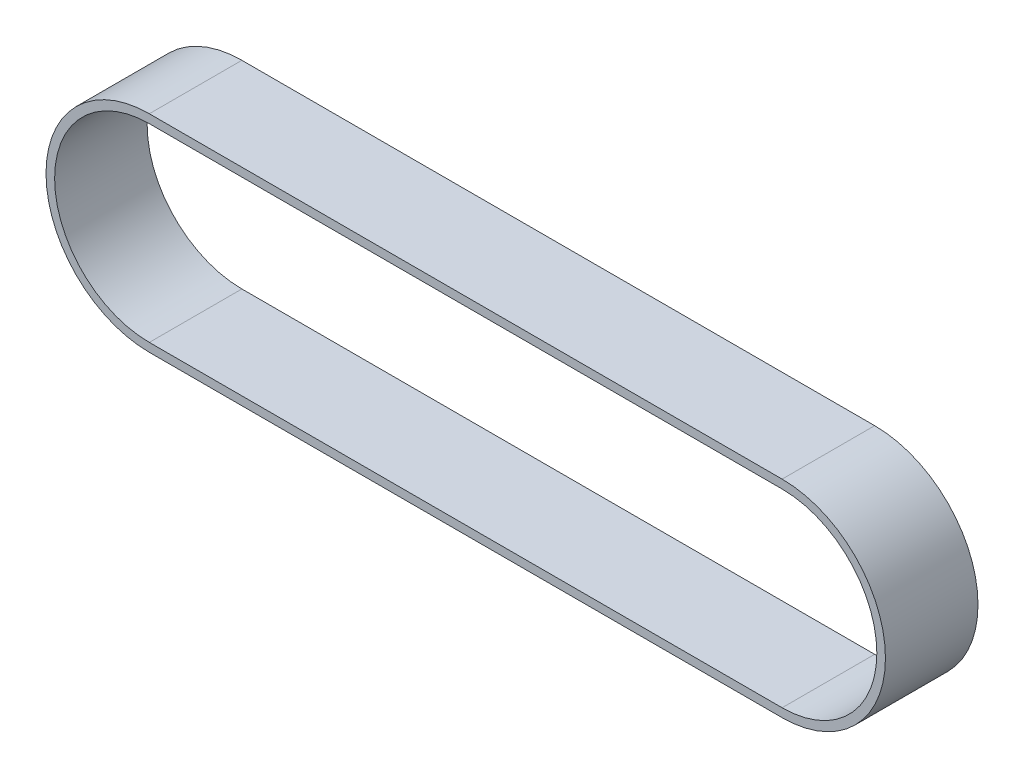
SolidWorks part; units mm, degrees
ref_plane "Front Plane" through (0, 0, 0) normal (0, 0, 1) x (1, 0, 0)
ref_plane "Top Plane" through (0, 0, 0) normal (0, 1, 0) x (1, 0, 0)
ref_plane "Right Plane" through (0, 0, 0) normal (1, 0, 0) x (0, 0, -1)
sketch "Sketch1" plane through (0, 0, 0) normal (0, 0, 1) x (1, 0, 0)
  line L0 (-50.4004, 0) -> (69.3544, 0) construction
  line L1 (0, 85.0776) -> (0, -72.5852) construction
  line L2 (-73.5, 0) -> (73.5, 0) construction
  line L3 (-73.5, 22) -> (73.5, 22)
  line L4 (-73.5, -22) -> (73.5, -22)
  line L5 (-73.5, 24) -> (73.5, 24)
  line L6 (-73.5, -24) -> (73.5, -24)
  arc A0 (73.5, -24) -> (73.5, 24) centre (73.5, 0) ccw
  arc A1 (-73.5, 24) -> (-73.5, -24) centre (-73.5, 0) ccw
  arc A2 (-73.5, 22) -> (-73.5, -22) centre (-73.5, 0) ccw
  arc A3 (73.5, -22) -> (73.5, 22) centre (73.5, 0) ccw
  point P11 (0, 0)
  dimension "D1" = 22
  dimension "D2" = 2
  dimension "D3" = 147
extrude "Boss-Extrude1" add sketch "Sketch1" along normal blind 21.5
